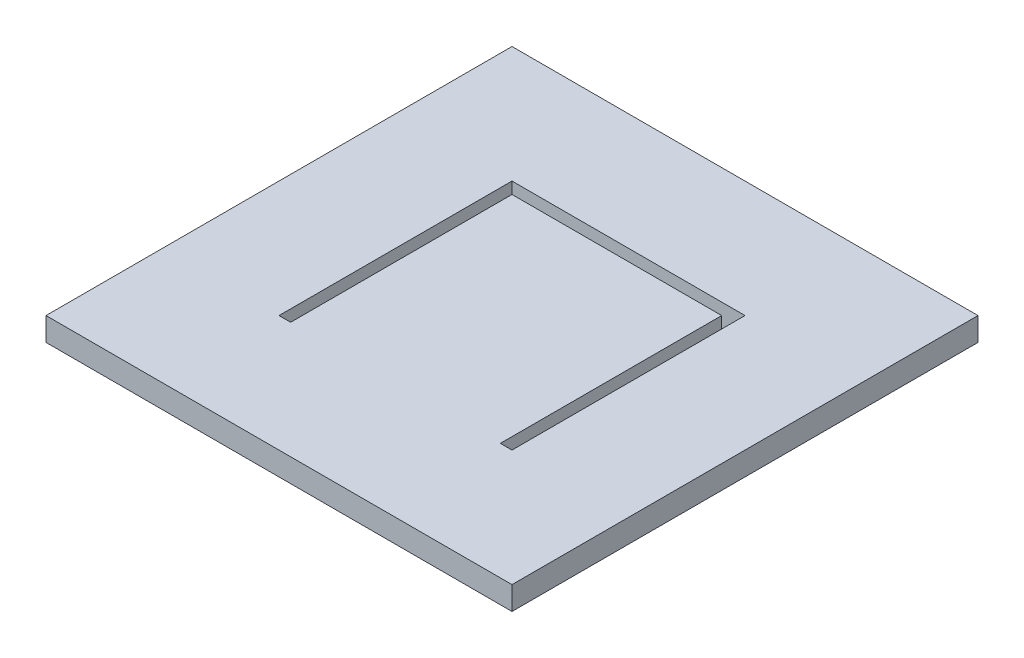
SolidWorks part; units mm, degrees
ref_plane "前基準面" through (0, 0, 0) normal (0, 0, 1) x (1, 0, 0)
ref_plane "上基準面" through (0, 0, 0) normal (0, 1, 0) x (1, 0, 0)
ref_plane "右基準面" through (0, 0, 0) normal (1, 0, 0) x (0, 0, -1)
sketch "草圖1" plane through (0, 0, 0) normal (0, 1, 0) x (1, 0, 0)
  line L0 (-50, -50) -> (-50, 50)
  line L1 (-100, -100) -> (100, -100)
  line L2 (-100, -100) -> (-100, 100)
  line L3 (-100, 100) -> (100, 100)
  line L4 (100, -100) -> (100, 100)
  line L5 (-100, -100) -> (100, 100) construction
  line L6 (-100, 100) -> (100, -100) construction
  line L7 (-50, 50) -> (50, 50)
  line L8 (50, 50) -> (50, -50)
  point P0 (0, 0)
  point P9 (0, 0)
  dimension "D1" = 200
  dimension "D2" = 200
  dimension "D3" = 100
extrude "填料-伸長1" add sketch "草圖1" against normal blind 10 contours L1 L4 L3 L2 region at (0, 0, 0)
extrude "除料-伸長-薄件1" cut sketch "草圖1<3>" against normal blind 10 thin contours L0 L7 L8 thin type one direction wall 5
sketch "草圖1<3>" plane through (0, 0, 0) normal (0, 1, 0) x (1, 0, 0) same geometry as "草圖1"
